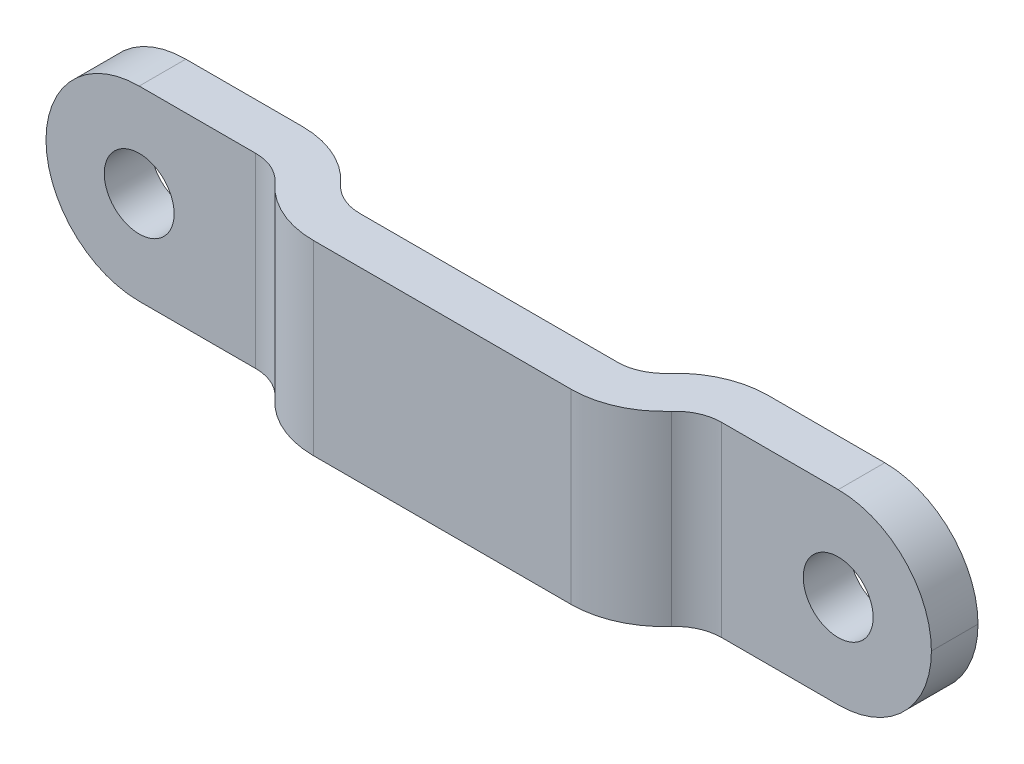
SolidWorks part; units mm, degrees
material "Nickel"
ref_plane "front" through (0, 0, 0) normal (0, 0, 1) x (1, 0, 0)
ref_plane "top" through (0, 0, 0) normal (0, 1, 0) x (1, 0, 0)
ref_plane "side" through (0, 0, 0) normal (1, 0, 0) x (0, 0, -1)
sketch "Sketch1" plane through (0, 0, 0) normal (0, 1, 0) x (1, 0, 0)
  line L0 (-30.1625, 0) -> (-15.875, 0)
  line L1 (-30.1625, 0) -> (-30.1625, -3.175)
  line L2 (-30.1625, -3.175) -> (-15.875, -3.175)
  line L3 (-8.7755, -6.35) -> (8.7755, -6.35)
  line L4 (0, 0) -> (0, 21.9313) construction
  line L5 (-8.7755, -3.175) -> (8.7755, -3.175)
  line L6 (30.1625, -3.175) -> (15.875, -3.175)
  line L7 (30.1625, 0) -> (30.1625, -3.175)
  line L8 (30.1625, 0) -> (15.875, 0)
  line L9 (-50, 0) -> (50, 0) construction
  arc A0 (-15.875, -3.175) -> (-13.5085, -4.2333) centre (-15.875, -6.35) cw
  arc A1 (-13.5085, -4.2333) -> (-8.7755, -6.35) centre (-8.7755, 0) ccw
  arc A2 (-15.875, 0) -> (-11.142, -2.1167) centre (-15.875, -6.35) cw
  arc A3 (-11.142, -2.1167) -> (-8.7755, -3.175) centre (-8.7755, 0) ccw
  arc A4 (11.142, -2.1167) -> (8.7755, -3.175) centre (8.7755, 0) cw
  arc A5 (15.875, 0) -> (11.142, -2.1167) centre (15.875, -6.35) ccw
  arc A6 (13.5085, -4.2333) -> (8.7755, -6.35) centre (8.7755, 0) cw
  arc A7 (15.875, -3.175) -> (13.5085, -4.2333) centre (15.875, -6.35) ccw
  dimension "D5" = 6.35
  dimension "D3" = 6.35
  dimension "D1" = 3.175
  dimension "D2" = 60.325
  dimension "D4" = 31.75
  dimension "D7" = 3.175
extrude "Base-Extrude" add sketch "Sketch1" along normal mid plane 12.7
fillet "Fillet1" radius 6.35 4 edges at (30.1625, 6.35, 1.5875) (30.1625, -6.35, 1.5875) (-30.1625, 6.35, 1.5875) (-30.1625, -6.35, 1.5875)
sketch "Sketch2" plane through (0, 0, 3.175) normal (0, 0, 1) x (1, 0, 0)
  circle A0 centre (23.8125, 0) radius 2.3813
  circle A1 centre (-23.8125, 0) radius 2.3813
  arc A2 (30.1625, 0) -> (23.8125, 6.35) centre (23.8125, 0) ccw construction
  arc A3 (-23.8125, 6.35) -> (-30.1625, 0) centre (-23.8125, 0) ccw construction
  dimension "D1" = 4.7625
extrude "Cut-Extrude1" cut sketch "Sketch2" against normal through all
